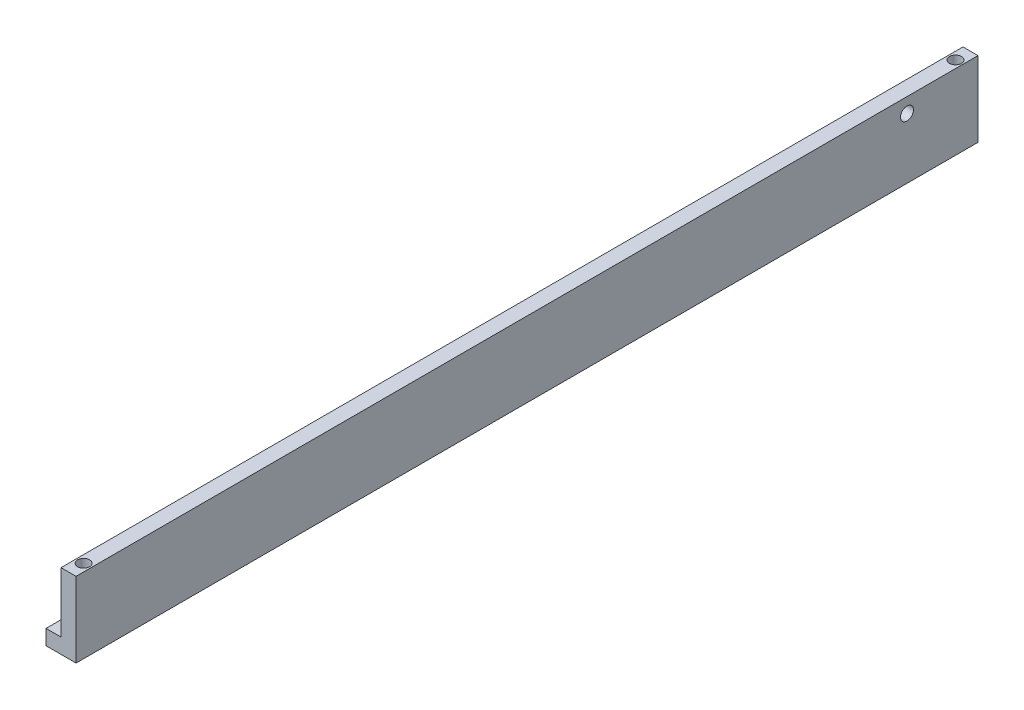
SolidWorks part; units mm, degrees
other "Markup1"
sketch "Sketch6" plane through (0, 0, 0) normal (0.1266, -0.8901, -0.4379) x (-0.2811, -0.4555, 0.8447)
ref_plane "Front Plane" through (0, 0, 0) normal (0, 0, 1) x (1, 0, 0)
ref_plane "Top Plane" through (0, 0, 0) normal (0, 1, 0) x (1, 0, 0)
ref_plane "Right Plane" through (0, 0, 0) normal (1, 0, 0) x (0, 0, -1)
sketch "Sketch1" plane through (0, 0, 0) normal (0, 0, 1) x (1, 0, 0)
  line L0 (0, 0) -> (-6.35, 0)
  line L3 (-6.35, 0) -> (-6.35, 31.75)
  line L4 (-6.35, 31.75) -> (0, 31.75)
  line L5 (0, 31.75) -> (0, 0)
  dimension "D1" = 31.75
  dimension "D4" = 6.35
extrude "Boss-Extrude1" add sketch "Sketch1" along normal blind 381 contours L3 L0 L5 L4 region at (-3.175, 15.875, 0)
sketch "Sketch2" plane through (0, 31.75, 0) normal (0, 1, 0) x (1, 0, 0)
  line L0 (-3.175, 0) -> (-3.175, -381) construction
  line L3 (-6.35, 0) -> (0, 0) construction
  line L4 (-6.35, -381) -> (0, -381) construction
  circle A0 centre (-3.175, -374.65) radius 2.54
  circle A1 centre (-3.175, -6.35) radius 2.54
  dimension "D1" = 5.08
  dimension "D2" = 6.35
  dimension "D3" = 6.35
sketch "Sketch3" plane through (0, 0, 0) normal (0, -1, 0) x (1, 0, 0)
  line L0 (-3.175, 0) -> (-3.175, 381) construction
  line L3 (0, 381) -> (0, 0) construction
  line L4 (0, 0) -> (-6.35, 0) construction
  line L5 (0, 381) -> (-6.35, 381) construction
  circle A0 centre (-3.175, 374.65) radius 2.54
  circle A1 centre (-3.175, 6.35) radius 2.54
  dimension "D2" = 5.08
  dimension "D1" = 3.175
  dimension "D3" = 6.35
  dimension "D4" = 6.35
sketch "Sketch4" plane through (0, 0, 0) normal (1, 0, 0) x (0, 0, -1)
  line L1 (-381, 31.75) -> (-381, 0) construction
  line L3 (-381, 31.75) -> (0, 31.75) construction
  circle A0 centre (-15.24, 24.765) radius 3.175
  dimension "D3" = 6.35
  dimension "D1" = 365.76
  dimension "D2" = 6.985
extrude "Boss-Extrude2" add sketch "Sketch1<3>" along normal blind 25.4 contours L0 region at (-3.175, 15.875, 0)
sketch "Sketch1<3>" plane through (0, 0, 0) normal (0, 0, 1) x (1, 0, 0) same geometry as "Sketch1"
sketch "Sketch5" plane through (0, 0, 381) normal (0, 0, 1) x (1, 0, 0)
  line L1 (-6.35, 0) -> (-12.7, 0)
  line L2 (-6.35, 0) -> (-6.35, 6.35)
  line L3 (-6.35, 6.35) -> (-12.7, 6.35)
  line L4 (-12.7, 0) -> (-12.7, 6.35)
  dimension "D1" = 6.35
  dimension "D2" = 6.35
extrude "Boss-Extrude3" add sketch "Sketch5" against normal blind 35.56
extrude "Cut-Extrude4" cut sketch "Sketch2" against normal blind 7.62
extrude "Cut-Extrude5" cut sketch "Sketch3" against normal blind 7.62
sketch "Sketch7" plane through (0, 0, 0) normal (1, 0, 0) x (0, 0, -1)
  circle A1 centre (-30, 25.5625) radius 2.75
  circle A2 centre (-30, 25.5625) radius 2.75
  dimension "D1" = 0
extrude "Cut-Extrude6" cut sketch "Sketch7" against normal through all
